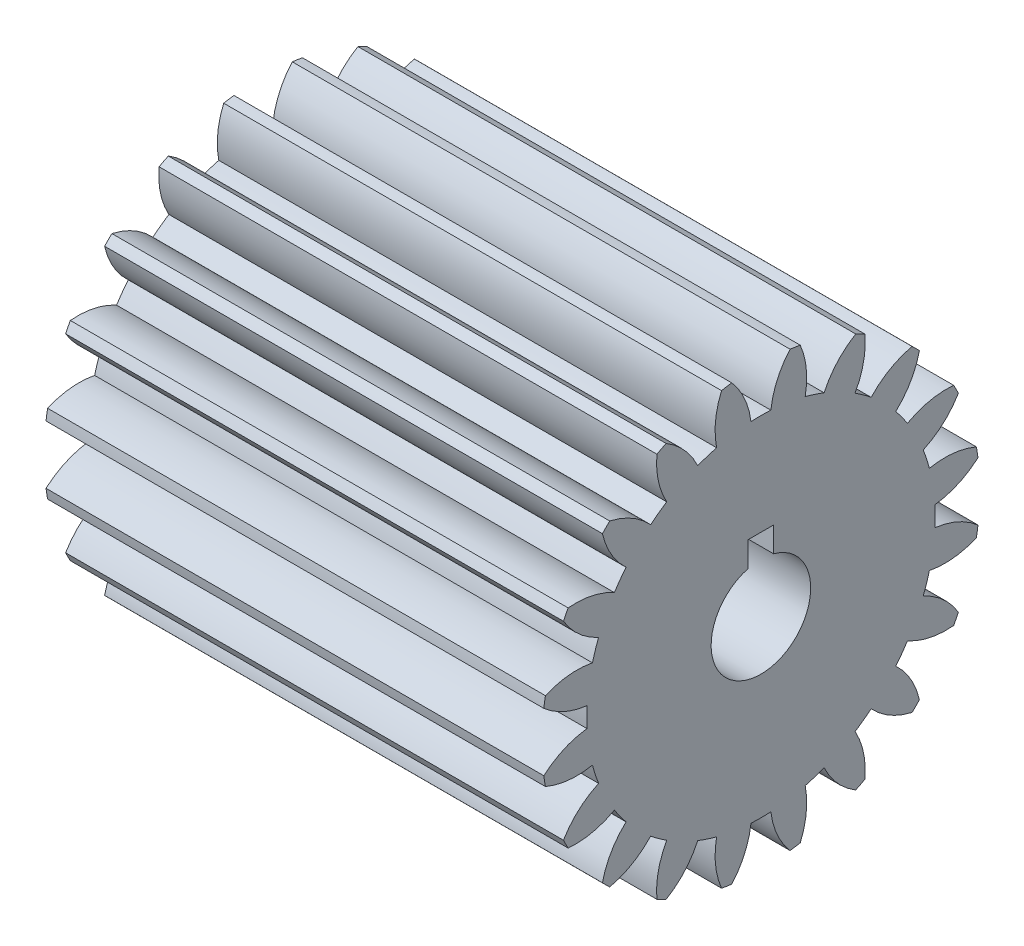
SolidWorks part; units mm, degrees
ref_plane "Plane1" through (0, 0, 0) normal (0, 0, 1) x (1, 0, 0)
ref_plane "Plane2" through (0, 0, 0) normal (0, 1, 0) x (1, 0, 0)
ref_plane "Plane3" through (0, 0, 0) normal (1, 0, 0) x (0, 0, -1)
other "Configuration Table"
sketch "HoldingSke" plane through (0, 0, 0) normal (0, 1, 0) x (1, 0, 0)
  line L0 (0, 0) -> (2.3492, -0.8551)
  line L1 (-15, 0) -> (100, 0) construction
  line L2 (0, 0) -> (-2.1039, 2.3779)
  line L3 (0, 0) -> (-11.863, 4.5341)
  line L4 (0, 0) -> (8.1152, 2.9537)
  line L5 (0, 0) -> (-46.8476, -17.4728)
  line L6 (0, 0) -> (-8.2896, -5.593)
  line L7 (-2.1039, 2.3779) -> (8.6586, 51.2059)
  line L8 (-76.2, 54.61) -> (-75.9, 54.61)
  line L9 (-71.009, 38.7566) -> (-53.1078, 45.2721)
  line L10 (-76.2, 71.12) -> (104.1128, 71.12)
  line L11 (0, 0) -> (-10, 0)
  line L12 (-76.2, 101.6) -> (-76.185, 101.6)
  line L13 (24.9733, 27.94) -> (52.9518, 28.4284)
  line L14 (24.9733, 27.94) -> (24.9743, 27.94)
  line L15 (24.9733, 27.94) -> (100.4006, 29.5858)
  line L16 (-63.627, -0.4) -> (-12.827, -0.4)
  circle A0 centre (0, 0) radius 1
  circle A1 centre (0, 0) radius 3.499
  circle A2 centre (0, 0) radius 37.5
  circle A3 centre (0, 0) radius 1
  dimension "Num_teeth" = 20
  dimension "Pitch_radius" = 180.3128
  dimension "Width" = 10
  dimension "Thickness" = 10
sketch "BasProSke" plane through (0, 0, 0) normal (0, 1, 0) x (1, 0, 0)
  line L0 (-10, 0) -> (60, 0) construction
  line L1 (0, 0) -> (0, 4.4)
  line L2 (0, 0) -> (10, 0)
  line L3 (10, 0) -> (10, 4.4)
  line L4 (10, 4.4) -> (0, 4.4)
  dimension "Thickness" = 10
  dimension "Diameter" = 8.8
revolve "Base-Revolve" add sketch "BasProSke" angle 360 about L0
sketch "TooCutSke" plane through (0, 0, 0) normal (1, 0, 0) x (0, 0, -1)
  line L1 (0, 0) -> (0, 107) construction
  line L2 (0, 0) -> (-0.3401, 3.9855) construction
  line L3 (0, 0) -> (-1.2482, 7.8811) construction
  line L4 (-0.3401, 3.9855) -> (-0.6241, 3.9405) construction
  arc A0 (0.1996, 3.4933) -> (-0.1996, 3.4933) centre (0, 0) ccw
  arc A1 (0.606, 4.3837) -> (-0.606, 4.3837) centre (0, 0) ccw
  circle A2 centre (0, 0) radius 4 construction
  circle A3 centre (0, 0) radius 3.7588 construction
  arc A4 (-0.1996, 3.4933) -> (-0.606, 4.3837) centre (-1.7886, 3.306) ccw
  arc A5 (0.606, 4.3837) -> (0.1996, 3.4933) centre (1.7886, 3.306) ccw
extrude "ToothCut" cut sketch "TooCutSke" along normal through all
fillet "Breaks" [suppressed] radius 0.008 tangent propagation no
fillet "RootFillets" [suppressed] radius 0.101
pattern_circular "TeethCuts" count 20 every 18 about axis through (-10, 0, 0) along (1, 0, 0) of "ToothCut", "RootFillets", "Breaks"
sketch "HubNeaOneSke" plane through (0, 0, 0) normal (-1, 0, 0) x (0, 0, 1)
  circle A0 centre (0, 0) radius 3.499
  dimension "Diameter" = 6.998
extrude "HubNearOne" [suppressed] add sketch "HubNeaOneSke" along normal blind 40.0001
sketch "HubNeaBotSke" plane through (0, 0, 0) normal (-1, 0, 0) x (0, 0, 1)
  circle A0 centre (0, 0) radius 3.499
  dimension "Diameter" = 6.998
extrude "HubNearBoth" [suppressed] add sketch "HubNeaBotSke" along normal blind 20
ref_plane "FarPln" through (10, 0, 0) normal (1, 0, 0) x (0, 0, -1)
sketch "HubFarSke" plane through (10, 0, 0) normal (1, 0, 0) x (0, 0, -1)
  circle A0 centre (0, 0) radius 3.499
  dimension "Diameter" = 6.998
extrude "HubFar" [suppressed] add sketch "HubFarSke" along normal blind 20
sketch "BorSke" plane through (0, 0, 0) normal (1, 0, 0) x (0, 0, -1)
  circle A0 centre (0, 0) radius 1
  dimension "Diameter" = 2
extrude "Bore" cut sketch "BorSke" along normal mid plane 100.0001
sketch "KeySke" plane through (0, 0, 0) normal (1, 0, 0) x (0, 0, -1)
  line L0 (-0.4, 0) -> (-0.4, 1.3)
  line L1 (-0.4, 1.3) -> (0.4, 1.3)
  line L2 (0.4, 1.3) -> (0.4, 0)
  line L3 (0, 0) -> (0, 34) construction
  line L4 (-0.4, 0) -> (0.4, 0)
  dimension "Width" = 0.8
extrude "Keyway" [suppressed] cut sketch "KeySke" along normal mid plane 100.0001
pattern_circular "Keyway2" [suppressed] count 2 every 90 about axis through (-10, 0, 0) along (1, 0, 0) reverse direction yes
sketch "Sketch1" plane through (10, 0, 0) normal (1, 0, 0) x (0, 0, -1)
  line L0 (-0.255, 0.9587) -> (0.255, 0.9587)
  line L1 (-0.255, 0.9587) -> (-0.255, 1.4687)
  line L2 (0.255, 0.9587) -> (0.255, 1.4687)
  line L3 (-0.255, 1.4687) -> (0.255, 1.4687)
  line L4 (0.9587, 0.255) -> (0.9587, -0.255)
  line L5 (0.9587, 0.255) -> (1.4687, 0.255)
  line L6 (0.9587, -0.255) -> (1.4687, -0.255)
  line L7 (1.4687, 0.255) -> (1.4687, -0.255)
  line L8 (0.3956, -0.9097) -> (-0.3956, -0.9097)
  line L9 (0.3956, -0.9097) -> (0.3956, -1.7497)
  line L10 (-0.3956, -0.9097) -> (-0.3956, -1.7497)
  line L11 (0.3956, -1.7497) -> (-0.3956, -1.7497)
  line L12 (-0.9152, -0.3827) -> (-0.9152, 0.3827)
  line L13 (-0.9152, -0.3827) -> (-1.7156, -0.3827)
  line L14 (-0.9152, 0.3827) -> (-1.7156, 0.3827)
  line L15 (-1.7156, -0.3827) -> (-1.7156, 0.3827)
  circle A0 centre (0, 0) radius 0.992
  dimension "D2" = 1.984
  dimension "D1" = 0.51
  dimension "D3" = 0.51
  dimension "D4" = 0.51
  dimension "D5" = 0.51
extrude "Cut-Extrude1" cut sketch "Sketch1" against normal blind 100 contours L3 L2 L0 L1
equation "' \"Module@HoldingSke\" = 6.35"
equation "' \"Num_teeth@HoldingSke\" = 12"
equation "' \"Ap@HoldingSke\" =  20"
equation "' \"Ap@HoldingSke\" = 20"
equation "' \"Width@HoldingSke\" = 0.5 * 25.4"
equation "' \"Hub_dia@HoldingSke\"= 1 * 25.4"
equation "' \"Hub_dia@HoldingSke\" = 1 * 25.4"
equation "' \"Overall_len@HoldingSke\" = 1.0 * 25.4"
equation "' \"Bore@HoldingSke\" = 0.75 * 25.4"
equation "' \"T_dim@HoldingSke\" = 0.1 * 25.4"
equation "' \"Width@KeySke\" = 0.25 * 25.4"
equation "' \"Show_teeth@HoldingSke\" = 13"
equation "' \"Backlash@HoldingSke\" = 0.009 * 25.4"
equation "' \"Addendum_fac@HoldingSke\" = 1.0"
equation "' \"Dedendum_fac@HoldingSke\" = 1.25"
equation "' \"Dedendum_add@HoldingSke\" = 0.00005 * 25.4"
equation "' \"Clearance_fac@HoldingSke\" = 0.25"
equation "\"Pitch@HoldingSke\" = 1 / \"Module@HoldingSke\""
equation "\"Overcut_dia@TooCutSke\" = (\"Num_teeth@HoldingSke\" + 2 * \"Addendum_fac@HoldingSke\") / \"Pitch@HoldingSke\" + 0.002 * 25.4"
equation "\"Pitch_dia@TooCutSke\" = \"Num_teeth@HoldingSke\" / \"Pitch@HoldingSke\""
equation "\"Base_dia@TooCutSke\" = \"Num_teeth@HoldingSke\" / \"Pitch@HoldingSke\" * cos((\"Ap@HoldingSke\"  * 3.14159265 / 180))"
equation "\"Root_dia@TooCutSke\" = (\"Num_teeth@HoldingSke\" + 2) / \"Pitch@HoldingSke\" - 2 * (\"Addendum_fac@HoldingSke\" + \"Dedendum_fac@HoldingSke\") / \"Pitch@HoldingSke\" - \"Dedendum_add@HoldingSke\" * 2"
equation "\"Half_ang@TooCutSke\" = 180 / \"Num_teeth@HoldingSke\""
equation "\"Half_CT@TooCutSke\" = \"Num_teeth@HoldingSke\" / \"Pitch@HoldingSke\" * sin((3.14159265 / 2 / \"Num_teeth@HoldingSke\")) / 2 - 7 * \"Backlash@HoldingSke\" / 4"
equation "\"Flank_rad@TooCutSke\" = \"Num_teeth@HoldingSke\" / \"Pitch@HoldingSke\" / 5"
equation "\"Radius@RootFillets\" = \"Clearance_fac@HoldingSke\" / \"Pitch@HoldingSke\" + \"Dedendum_add@HoldingSke\""
equation "\"Break_rad@Breaks\" = 0.02 / \"Pitch@HoldingSke\""
equation "\"Thickness@HoldingSke\" = \"Width@HoldingSke\""
equation "\"OAL@HoldingSke\" = \"Thickness@HoldingSke\""
equation "\"MHD@HoldingSke\" = (\"Num_teeth@HoldingSke\" + 2) / \"Pitch@HoldingSke\" - 2 * (\"Addendum_fac@HoldingSke\" + \"Dedendum_fac@HoldingSke\")  / \"Pitch@HoldingSke\" - \"Dedendum_add@HoldingSke\" * 2"
equation "\"MBD@HoldingSke\" = (\"Num_teeth@HoldingSke\" + 2) / \"Pitch@HoldingSke\" - 2 * (\"Addendum_fac@HoldingSke\" + \"Dedendum_fac@HoldingSke\")  / \"Pitch@HoldingSke\" - \"Dedendum_add@HoldingSke\" * 2 - 0.002 * 25.4"
equation "\"MHD@HoldingSke\" = ((sgn( \"MHD@HoldingSke\" - \"Hub_dia@HoldingSke\" )-1)*( \"MHD@HoldingSke\" - \"Hub_dia@HoldingSke\" ))/-2+ \"Hub_dia@HoldingSke\""
equation "\"MBD@HoldingSke\" = ((sgn( \"MBD@HoldingSke\" - \"Bore@HoldingSke\" )-1)*( \"MBD@HoldingSke\" - \"Bore@HoldingSke\" ))/-2+ \"Bore@HoldingSke\""
equation "\"OAL@HoldingSke\" = ((sgn( \"OAL@HoldingSke\" - \"Overall_len@HoldingSke\" )+1)*( \"OAL@HoldingSke\" - \"Overall_len@HoldingSke\" ))/2 + \"Overall_len@HoldingSke\" + 0.000002 * 25.4"
equation "\"Num_teeth@TeethCuts\" = int( \"Show_teeth@HoldingSke\" ) + 1"
equation "\"Num_teeth@TeethCuts\" = ((sgn( \"Num_teeth@TeethCuts\" - \"Num_teeth@HoldingSke\" )-1)*( \"Num_teeth@TeethCuts\" - \"Num_teeth@HoldingSke\" ))/-2+ \"Num_teeth@HoldingSke\""
equation "\"Num_teeth@TeethCuts\" = ((sgn( \"Num_teeth@TeethCuts\" - 2.0)+1)*( \"Num_teeth@TeethCuts\" - 2.0))/2 +2.0"
equation "\"Angle@TeethCuts\" = 360.0 / \"Num_teeth@HoldingSke\""
equation "\"Diameter@BasProSke\" = (\"Num_teeth@HoldingSke\" + 2 * \"Addendum_fac@HoldingSke\") / \"Pitch@HoldingSke\""
equation "\"Thickness@BasProSke\"  = \"Thickness@HoldingSke\""
equation "' \"Fillet_rad@BasProSke\" =  \"Thickness@HoldingSke\" * 0.05"
equation "' \"Fillet_rad@BasProSke\" = \"Thickness@HoldingSke\" * 0.05"
equation "\"MHD@HoldingSke\" = ((sgn( \"MHD@HoldingSke\" - \"Root_dia@TooCutSke\" )-1)*( \"MHD@HoldingSke\" - \"Root_dia@TooCutSke\" ))/-2+ \"Root_dia@TooCutSke\""
equation "\"Diameter@HubNeaOneSke\" = \"MHD@HoldingSke\""
equation "\"Length@HubNearOne\" = \"OAL@HoldingSke\" - \"Thickness@BasProSke\""
equation "\"Diameter@HubNeaBotSke\" = \"MHD@HoldingSke\""
equation "\"Length@HubNearBoth\" = ( \"OAL@HoldingSke\" - \"Thickness@BasProSke\" ) / 2.0"
equation "\"Thickness@FarPln\" = \"Thickness@BasProSke\""
equation "\"Diameter@HubFarSke\" = \"MHD@HoldingSke\""
equation "\"Length@HubFar\" = ( \"OAL@HoldingSke\" - \"Thickness@BasProSke\" ) / 2.0"
equation "\"Diameter@BorSke\" = \"MBD@HoldingSke\""
equation "\"D1@Bore\" = \"OAL@HoldingSke\" * 2.0"
equation "\"D1@Keyway\" = \"OAL@HoldingSke\" * 2.0"
equation "\"Offset@KeySke\" = \"T_dim@HoldingSke\" + \"MBD@HoldingSke\" / 2.0"
